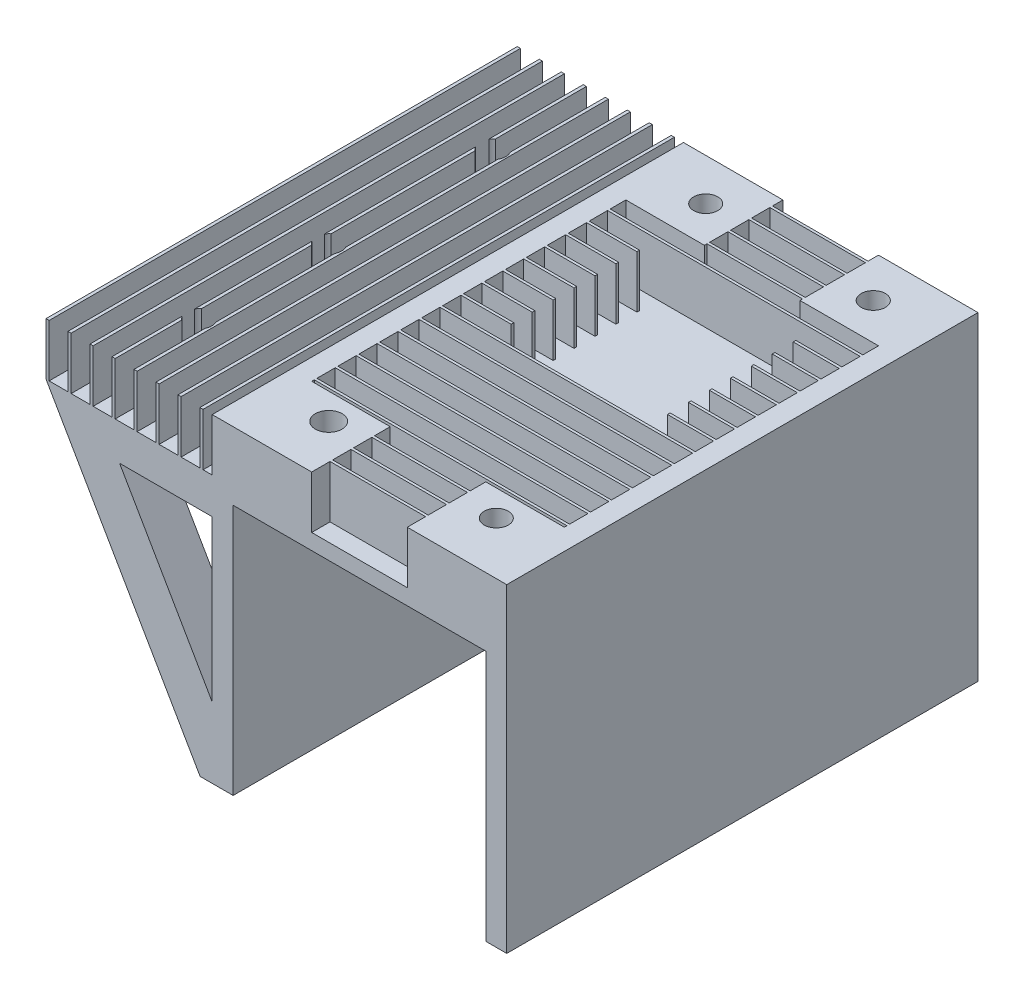
SolidWorks part; units mm, degrees
ref_plane "Front" through (0, 0, 0) normal (0, 0, 1) x (1, 0, 0)
ref_plane "Top" through (0, 0, 0) normal (0, 1, 0) x (1, 0, 0)
ref_plane "Right" through (0, 0, 0) normal (1, 0, 0) x (0, 0, -1)
sketch "Sketch1" plane through (0, 0, 0) normal (0, 0, 1) x (1, 0, 0)
  line L0 (0, 0) -> (0, 70)
  line L1 (0, 70) -> (56.254, 70)
  line L2 (56.254, 70) -> (56.254, 0)
  line L3 (56.254, 0) -> (52.254, 0)
  line L4 (52.254, 0) -> (52.254, 65)
  line L5 (52.254, 65) -> (4, 65)
  line L6 (4, 65) -> (4, 0)
  line L7 (4, 0) -> (0, 0)
  line L9 (4, 55) -> (52.254, 55)
  line L10 (4, 55) -> (4, 52)
  line L11 (4, 52) -> (52.254, 52)
  line L12 (52.254, 55) -> (52.254, 52)
  dimension "D1" = 48.254
  dimension "D2" = 4
  dimension "D3" = 4
  dimension "D4" = 5
  dimension "D5" = 70
  dimension "D6" = 3
  dimension "D7" = 10
extrude "Boss-Extrude1" add sketch "Sketch1" along normal blind 70 contours L7 L6 L5 L4 L3 L2 L1 L0 | L9 L12 L11 L10 region at (0.898, 35, 0)
sketch "Sketch3" plane through (0, 0, 70) normal (0, 0, 1) x (1, 0, 0)
  line L0 (0, 70) -> (-40.3946, 70)
  line L1 (-40.3946, 70) -> (0, 0.0344)
  line L2 (0, 0) -> (0, 70) construction
  line L3 (0, 0.0344) -> (0, 70)
  line L4 (0, 70) -> (0, 62.5)
  line L5 (0, 62.5) -> (-26, 62.5)
  line L6 (-26, 62.5) -> (0, 17.4667)
  line L7 (0, 17.4667) -> (0, 0.0344)
  line M11 (0, 70) -> (0, 0)
  dimension "D1" = 60
  dimension "D2" = 180
  dimension "D3" = 7.5
  dimension "D4" = 26
extrude "Boss-Extrude3" add sketch "Sketch3" against normal blind 8 contours L6 L5 L0 L1 M11 region at (-16.8587, 46.1047, 70)
sketch "Sketch4" plane through (0, 0, 0) normal (0, 0, -1) x (-1, 0, 0)
  line L0 (0, 70) -> (40.3946, 70)
  line L1 (40.3946, 70) -> (0, 0)
  line L2 (0, 0) -> (0, 17.4667)
  line L3 (0, 17.4667) -> (26, 62.5)
  line L4 (26, 62.5) -> (0, 62.5)
  line L5 (0, 62.5) -> (0, 70)
extrude "Boss-Extrude4" add sketch "Sketch4" against normal blind 8
ref_plane "Plane1" through (0, 0, 39) normal (0, 0, -1) x (-1, 0, 0)
sketch "Sketch5" plane through (0, 0, 39) normal (0, 0, -1) x (-1, 0, 0)
  line L0 (0, 62.5) -> (0, 70)
  line L1 (0, 70) -> (40.3946, 70)
  line L2 (40.3946, 70) -> (0, 0)
  line L3 (0, 0) -> (0, 17.4667)
  line L4 (0, 17.4667) -> (26, 62.5)
  line L5 (26, 62.5) -> (0, 62.5)
extrude "Boss-Extrude5" add sketch "Sketch5" along normal blind 8
sketch "Sketch6" plane through (0, 0, 0) normal (0, 0, -1) x (-1, 0, 0)
  line L5 (0, 62.5) -> (36.0666, 62.5)
  line L6 (0, 0) -> (40.3946, 70) construction
  line L7 (36.0666, 62.5) -> (40.3946, 70)
  line L8 (40.3946, 70) -> (0, 70)
  line L9 (40.3946, 70) -> (-56.254, 70) construction
  line L10 (0, 70) -> (0, 62.5)
  line L11 (-4, 0) -> (0, 0)
  line L12 (0, 0) -> (7.5019, 13)
  line L13 (7.5019, 13) -> (-4, 13)
  line L14 (-4, 52) -> (-4, 0) construction
  line L15 (-4, 13) -> (-4, 0)
  dimension "D1" = 13
extrude "Boss-Extrude6" add sketch "Sketch6" against normal blind 70
sketch "Sketch7" plane through (0, 0, 70) normal (0, 0, 1) x (1, 0, 0)
  line L0 (0, 17.4667) -> (0, 62.5) construction
  line L1 (-40.3946, 70) -> (0, 70)
  line L2 (-40.3946, 70) -> (-40.3946, 53)
  line L3 (-40.3946, 53) -> (0, 53)
  line L4 (0, 70) -> (0, 53)
  dimension "D1" = 17
extrude "Cut-Extrude3" cut sketch "Sketch7" against normal blind 70
sketch "Sketch8" plane through (0, 0, 0) normal (0, 0, -1) x (-1, 0, 0)
  line L1 (-4, 55) -> (-4, 52)
  line L2 (-4, 52) -> (-52.254, 52) construction
  line L3 (-4, 52) -> (30.0074, 52)
  line L4 (0, 0) -> (30.5845, 53) construction
  line L6 (30.0074, 52) -> (31.7386, 55)
  line L7 (31.7386, 55) -> (-4, 55)
  dimension "D1" = 180
extrude "Boss-Extrude7" add sketch "Sketch8" against normal blind 70
sketch "Sketch11" plane through (0, 0, 70) normal (0, 0, 1) x (1, 0, 0)
  line L0 (-31.7386, 55) -> (0, 0)
  line L3 (-31.7386, 55) -> (0, 55) construction
  line L4 (-27.289, 55) -> (-31.7386, 55)
  line L5 (-27.289, 55) -> (-3.0537, 13)
  line L6 (-3.0537, 13) -> (0, 0)
extrude "Boss-Extrude10" add sketch "Sketch11" against normal blind 8
sketch "Sketch12" plane through (0, 0, 70) normal (0, 0, 1) x (1, 0, 0)
  line L0 (-31.7386, 55) -> (-27.7598, 48.1051)
  line L1 (0, 0) -> (-31.7386, 55) construction
  line L2 (-27.7598, 48.1051) -> (0, 48.1051)
  line L3 (0, 17.4667) -> (0, 52) construction
  line L4 (0, 48.1051) -> (0, 55)
  line L5 (0, 55) -> (-31.7386, 55)
extrude "Boss-Extrude11" add sketch "Sketch12" against normal blind 70
sketch "Sketch13" plane through (0, 0, 0) normal (0, -1, 0) x (1, 0, 0)
  line L1 (67.4394, -10.6205) -> (-15.562, -10.6205)
  line L2 (67.4394, -10.6205) -> (67.4394, 77.2481)
  line L3 (67.4394, 77.2481) -> (-15.562, 77.2481)
  line L4 (-15.562, -10.6205) -> (-15.562, 77.2481)
extrude "Cut-Extrude4" cut sketch "Sketch13" against normal blind 4
sketch "Sketch14" plane through (0, 0, 70) normal (0, 0, 1) x (1, 0, 0)
  line L0 (-2.3083, 4) -> (-31.7386, 55)
  line L1 (-31.7386, 55) -> (0, 55)
  line L2 (0, 55) -> (0, 70)
  line L3 (0, 70) -> (56.254, 70)
  line L4 (56.254, 70) -> (56.254, 4)
  line L5 (56.254, 4) -> (52.254, 4)
  line L6 (52.254, 4) -> (52.254, 52)
  line L7 (52.254, 52) -> (4, 52)
  line L8 (4, 52) -> (4, 4)
  line L9 (4, 4) -> (-2.3083, 4)
  line L14 (-17.6891, 48.1051) -> (0, 48.1051)
  line L15 (52.254, 55) -> (4, 55)
  line L16 (52.254, 55) -> (52.254, 65)
  line L17 (52.254, 65) -> (4, 65)
  line L18 (4, 55) -> (4, 65)
  line L19 (-17.6891, 48.1051) -> (0, 48.1051) construction
  line L20 (0, 48.1051) -> (0, 17.4667)
  line L21 (0, 17.4667) -> (-17.6891, 48.1051)
extrude "Boss-Extrude12" add sketch "Sketch14" along normal blind 20
sketch "Sketch15" plane through (0, 0, 90) normal (0, 0, 1) x (1, 0, 0)
  line L0 (56.254, 4) -> (56.254, 70) construction
  line L1 (56.254, 65) -> (37.264, 65)
  line L2 (56.254, 65) -> (56.254, 55)
  line L3 (56.254, 55) -> (37.264, 55)
  line L4 (37.264, 65) -> (37.264, 55)
  line L5 (4, 55) -> (52.254, 55) construction
  dimension "D1" = 18.99
sketch "Sketch16" plane through (0, 0, 90) normal (0, 0, 1) x (1, 0, 0)
  line L1 (0, 70) -> (56.254, 70)
  line L2 (0, 70) -> (0, 65)
  line L3 (0, 65) -> (56.254, 65)
  line L4 (56.254, 70) -> (56.254, 65)
extrude "Cut-Extrude5" cut sketch "Sketch16" against normal blind 100
sketch "Sketch17" plane through (0, 65, 0) normal (0, 1, 0) x (1, 0, 0)
  line L1 (52.254, 0) -> (37.254, 0)
  line L2 (52.254, 0) -> (52.254, -15)
  line L3 (52.254, -15) -> (37.254, -15)
  line L4 (37.254, 0) -> (37.254, -15)
  line L5 (52.254, -90) -> (37.254, -90)
  line L6 (52.254, -90) -> (52.254, -75)
  line L7 (52.254, -75) -> (37.254, -75)
  line L8 (37.254, -90) -> (37.254, -75)
  dimension "D1" = 15
  dimension "D2" = 15
  dimension "D3" = 15
  dimension "D4" = 15
extrude "Boss-Extrude14" add sketch "Sketch17" against normal blind 13
sketch "Sketch21" plane through (0, 52, 0) normal (0, -1, 0) x (-1, 0, 0)
  circle A0 centre (-44.254, -80) radius 2.3
  circle A1 centre (-44.254, -8) radius 2.3
sketch "Sketch22" plane through (0, 52, 0) normal (0, -1, 0) x (1, 0, 0)
  line L1 (48.0965, 6.0036) -> (47.9041, 10.3295)
  line L2 (47.9041, 10.3295) -> (44.0617, 12.3259)
  line L3 (44.0617, 12.3259) -> (40.4115, 9.9964)
  line L4 (40.4115, 9.9964) -> (40.6039, 5.6705)
  line L5 (40.6039, 5.6705) -> (44.4463, 3.6741)
  line L6 (44.4463, 3.6741) -> (48.0965, 6.0036)
  line L7 (45.2007, 75.7746) -> (48.3866, 78.7072)
  line L8 (48.3866, 78.7072) -> (47.4399, 82.9325)
  line L9 (47.4399, 82.9325) -> (43.3073, 84.2254)
  line L10 (43.3073, 84.2254) -> (40.1214, 81.2928)
  line L11 (40.1214, 81.2928) -> (41.0681, 77.0675)
  line L12 (41.0681, 77.0675) -> (45.2007, 75.7746)
  circle A0 centre (44.254, 8) radius 3.75 construction
  circle A1 centre (44.254, 80) radius 3.75 construction
  point P10 (42.2366, 11.1611)
  dimension "D1" = 7.5
  dimension "D2" = 7.5
extrude "Cut-Extrude8" cut sketch "Sketch22" against normal blind 5
extrude "Cut-Extrude9" cut sketch "Sketch21" against normal blind 15
sketch "Sketch23" plane through (0, 0, 0) normal (-0.8661, -0.4998, 0) x (0, 0, 1)
  line L0 (90, 63.5007) -> (90, 4.6182) construction
  line L1 (70, 55.5401) -> (82, 55.5401)
  line L2 (70, 55.5401) -> (70, 15.0093)
  line L3 (70, 15.0093) -> (82, 15.0093)
  line L4 (82, 55.5401) -> (82, 15.0093)
  line L5 (62, 55.5401) -> (62, 15.0093) construction
  dimension "D1" = 8
  dimension "D2" = 8
extrude "Cut-Extrude10" cut sketch "Sketch23" against normal blind 9
sketch "Sketch25" plane through (0, 48.1051, 0) normal (0, -1, 0) x (-1, 0, 0)
  circle A0 centre (17.0755, -19.3006) radius 2.3
  circle A1 centre (17.0755, -50.6137) radius 2.3
extrude "Cut-Extrude11" cut sketch "Sketch25" against normal blind 20
sketch "Sketch26" plane through (0, 48.1051, 0) normal (0, -1, 0) x (1, 0, 0)
  circle A0 centre (-17.0755, 75.3913) radius 2.3
extrude "Cut-Extrude12" cut sketch "Sketch26" against normal blind 20
sketch "Sketch27" plane through (0, 0, 90) normal (0, 0, 1) x (1, 0, 0)
  line L0 (-23.3104, 48.1051) -> (-27.7598, 48.1051)
  line L1 (-31.7386, 55) -> (-2.3083, 4) construction
  line L2 (-27.7598, 48.1051) -> (-31.7386, 55)
  line L3 (-31.7386, 55) -> (-23.3104, 55)
  line L4 (0, 55) -> (-31.7386, 55) construction
  line L5 (-23.3104, 55) -> (-23.3104, 48.1051)
extrude "Boss-Extrude16" add sketch "Sketch27" against normal blind 20
sketch "Sketch28" plane through (0, 55, 0) normal (0, 1, 0) x (1, 0, 0)
  line L0 (4, -90) -> (37.254, -90) construction
  line L1 (4, 0) -> (19, 0)
  line L2 (4, 0) -> (4, -15)
  line L3 (4, -15) -> (19, -15)
  line L4 (19, 0) -> (19, -15)
  line L5 (4, -90) -> (19, -90)
  line L6 (4, -90) -> (4, -75)
  line L7 (4, -75) -> (19, -75)
  line L8 (19, -90) -> (19, -75)
  line L9 (4, 0) -> (4, -90) construction
  dimension "D1" = 15
  dimension "D2" = 15
  dimension "D3" = 15
  dimension "D4" = 15
extrude "Boss-Extrude17" add sketch "Sketch28" along normal blind 10
sketch "Sketch29" plane through (0, 52, 0) normal (0, -1, 0) x (-1, 0, 0)
  circle A0 centre (-12.254, -8) radius 2.3
  circle A1 centre (-12.254, -80) radius 2.3
extrude "Cut-Extrude13" cut sketch "Sketch29" against normal blind 20
sketch "Sketch30" plane through (0, 48.1051, 0) normal (0, -1, 0) x (1, 0, 0)
  line L1 (-27.7598, 70) -> (-17.3688, 70)
  line L2 (-27.7598, 70) -> (-27.7598, 82)
  line L3 (-27.7598, 82) -> (-17.3688, 82)
  line L4 (-17.3688, 70) -> (-17.3688, 82)
extrude "Boss-Extrude18" add sketch "Sketch30" against normal blind 5
sketch "Sketch31" plane through (0, 48.1051, 0) normal (0, -1, 0) x (1, 0, 0)
  circle A0 centre (-17.0755, 75.3913) radius 2.3
extrude "Cut-Extrude14" cut sketch "Sketch31" against normal blind 45
sketch "Sketch36" plane through (0, 55, 0) normal (0, 1, 0) x (1, 0, 0)
  line L0 (0, -90) -> (-31.7386, -90) construction
  line L1 (-31.7386, 0) -> (-31.1386, 0)
  line L2 (-31.7386, 0) -> (-31.7386, -90)
  line L3 (-31.7386, -90) -> (-31.1386, -90)
  line L4 (-31.1386, 0) -> (-31.1386, -90)
  line L5 (-27.5386, 0) -> (-27.5386, -90)
  line L6 (-27.5386, 0) -> (-26.9386, 0)
  line L7 (-26.9386, 0) -> (-26.9386, -90)
  line L8 (-27.5386, -90) -> (-26.9386, -90)
  line L9 (-23.3386, 0) -> (-23.3386, -90)
  line L10 (-23.3386, 0) -> (-22.7386, 0)
  line L11 (-22.7386, 0) -> (-22.7386, -90)
  line L12 (-23.3386, -90) -> (-22.7386, -90)
  line L13 (-19.1386, 0) -> (-19.1386, -90)
  line L14 (-19.1386, 0) -> (-18.5386, 0)
  line L15 (-18.5386, 0) -> (-18.5386, -90)
  line L16 (-19.1386, -90) -> (-18.5386, -90)
  line L17 (-14.9386, 0) -> (-14.9386, -90)
  line L18 (-14.9386, 0) -> (-14.3386, 0)
  line L19 (-14.3386, 0) -> (-14.3386, -90)
  line L20 (-14.9386, -90) -> (-14.3386, -90)
  line L21 (-10.7386, 0) -> (-10.7386, -90)
  line L22 (-10.7386, 0) -> (-10.1386, 0)
  line L23 (-10.1386, 0) -> (-10.1386, -90)
  line L24 (-10.7386, -90) -> (-10.1386, -90)
  line L25 (-6.5386, 0) -> (-6.5386, -90)
  line L26 (-6.5386, 0) -> (-5.9386, 0)
  line L27 (-5.9386, 0) -> (-5.9386, -90)
  line L28 (-6.5386, -90) -> (-5.9386, -90)
  line L29 (-2.3386, 0) -> (-2.3386, -90)
  line L30 (-2.3386, 0) -> (-1.7386, 0)
  line L31 (-1.7386, 0) -> (-1.7386, -90)
  line L32 (-2.3386, -90) -> (-1.7386, -90)
  line L33 (-31.7386, 0) -> (-27.5386, 0) construction
  dimension "D1" = 0.6
  dimension "D3" = 4.2
  dimension "D2" = 8
extrude "Boss-Extrude19" add sketch "Sketch36" along normal blind 10
sketch "Sketch37" plane through (0, 55, 0) normal (0, 1, 0) x (1, 0, 0)
  line L0 (19, 0) -> (37.254, 0) construction
  line L13 (4, -6) -> (4, -6.5)
  line L14 (4, -15) -> (4, -75) construction
  line L15 (4, -2) -> (53, -2)
  line L16 (4, -2) -> (4, -2.5)
  line L17 (4, -2.5) -> (53, -2.5)
  line L18 (53, -2) -> (53, -2.5)
  line L19 (4, -6) -> (53, -6)
  line L20 (53, -6) -> (53, -6.5)
  line L21 (4, -6.5) -> (53, -6.5)
  line L22 (4, -10) -> (4, -10.5)
  line L23 (4, -10) -> (53, -10)
  line L24 (53, -10) -> (53, -10.5)
  line L25 (4, -10.5) -> (53, -10.5)
  line L26 (4, -14) -> (4, -14.5)
  line L27 (4, -14) -> (53, -14)
  line L28 (53, -14) -> (53, -14.5)
  line L29 (4, -14.5) -> (53, -14.5)
  line L30 (4, -18) -> (4, -18.5)
  line L31 (4, -18) -> (53, -18)
  line L32 (53, -18) -> (53, -18.5)
  line L33 (4, -18.5) -> (53, -18.5)
  line L34 (4, -22) -> (4, -22.5)
  line L35 (4, -22) -> (53, -22)
  line L36 (53, -22) -> (53, -22.5)
  line L37 (4, -22.5) -> (53, -22.5)
  line L38 (4, -26) -> (4, -26.5)
  line L39 (4, -26) -> (53, -26)
  line L40 (53, -26) -> (53, -26.5)
  line L41 (4, -26.5) -> (53, -26.5)
  line L42 (4, -30) -> (4, -30.5)
  line L43 (4, -30) -> (53, -30)
  line L44 (53, -30) -> (53, -30.5)
  line L45 (4, -30.5) -> (53, -30.5)
  line L46 (4, -34) -> (4, -34.5)
  line L47 (4, -34) -> (53, -34)
  line L48 (53, -34) -> (53, -34.5)
  line L49 (4, -34.5) -> (53, -34.5)
  line L50 (4, -38) -> (4, -38.5)
  line L51 (4, -38) -> (53, -38)
  line L52 (53, -38) -> (53, -38.5)
  line L53 (4, -38.5) -> (53, -38.5)
  line L54 (4, -42) -> (4, -42.5)
  line L55 (4, -42) -> (53, -42)
  line L56 (53, -42) -> (53, -42.5)
  line L57 (4, -42.5) -> (53, -42.5)
  line L58 (4, -46) -> (4, -46.5)
  line L59 (4, -46) -> (53, -46)
  line L60 (53, -46) -> (53, -46.5)
  line L61 (4, -46.5) -> (53, -46.5)
  line L62 (4, -50) -> (4, -50.5)
  line L63 (4, -50) -> (53, -50)
  line L64 (53, -50) -> (53, -50.5)
  line L65 (4, -50.5) -> (53, -50.5)
  line L66 (4, -54) -> (4, -54.5)
  line L67 (4, -54) -> (53, -54)
  line L68 (53, -54) -> (53, -54.5)
  line L69 (4, -54.5) -> (53, -54.5)
  line L70 (4, -58) -> (4, -58.5)
  line L71 (4, -58) -> (53, -58)
  line L72 (53, -58) -> (53, -58.5)
  line L73 (4, -58.5) -> (53, -58.5)
  line L74 (4, -62) -> (4, -62.5)
  line L75 (4, -62) -> (53, -62)
  line L76 (53, -62) -> (53, -62.5)
  line L77 (4, -62.5) -> (53, -62.5)
  line L78 (4, -66) -> (4, -66.5)
  line L79 (4, -66) -> (53, -66)
  line L80 (53, -66) -> (53, -66.5)
  line L81 (4, -66.5) -> (53, -66.5)
  line L82 (4, -70) -> (4, -70.5)
  line L83 (4, -70) -> (53, -70)
  line L84 (53, -70) -> (53, -70.5)
  line L85 (4, -70.5) -> (53, -70.5)
  line L86 (4, -74) -> (4, -74.5)
  line L87 (4, -74) -> (53, -74)
  line L88 (53, -74) -> (53, -74.5)
  line L89 (4, -74.5) -> (53, -74.5)
  line L90 (4, -78) -> (4, -78.5)
  line L91 (4, -78) -> (53, -78)
  line L92 (53, -78) -> (53, -78.5)
  line L93 (4, -78.5) -> (53, -78.5)
  line L94 (4, -82) -> (4, -82.5)
  line L95 (4, -82) -> (53, -82)
  line L96 (53, -82) -> (53, -82.5)
  line L97 (4, -82.5) -> (53, -82.5)
  line L98 (4, -86) -> (4, -86.5)
  line L99 (4, -86) -> (53, -86)
  line L100 (53, -86) -> (53, -86.5)
  line L101 (4, -86.5) -> (53, -86.5)
  dimension "D1" = 49
  dimension "D2" = 0.5
  dimension "D3" = 2
  dimension "D4" = 22
extrude "Boss-Extrude20" add sketch "Sketch37" along normal blind 10
sketch "Sketch39" plane through (0, 65, 0) normal (0, 1, 0) x (1, 0, 0)
  line L1 (13.6092, -19.7718) -> (43.455, -19.7718)
  line L2 (13.6092, -19.7718) -> (13.6092, -48.773)
  line L3 (13.6092, -48.773) -> (43.455, -48.773)
  line L4 (43.455, -19.7718) -> (43.455, -48.773)
  circle A0 centre (12.254, -8) radius 2.3
  circle A1 centre (44.254, -8) radius 2.3
  circle A2 centre (-17.0755, -19.3006) radius 2.4421
  circle A3 centre (-17.0755, -50.6137) radius 2.2138
  circle A4 centre (-17.0755, -75.3913) radius 2.3
  circle A5 centre (12.254, -80) radius 2.3
  circle A6 centre (44.254, -80) radius 2.3
extrude "Cut-Extrude15" cut sketch "Sketch39" against normal blind 10
sketch "Sketch40" plane through (0, 65, 0) normal (0, 1, 0) x (1, 0, 0)
  circle A0 centre (-17.0755, -19.3006) radius 2.2732
  circle A1 centre (-17.0755, -50.6137) radius 2.3827
  circle A2 centre (-17.0755, -75.3913) radius 2.3828
  circle A3 centre (12.254, -80) radius 2.5607
  circle A4 centre (44.254, -80) radius 2.2791
  circle A5 centre (44.254, -8) radius 2.3112
  circle A6 centre (12.254, -8) radius 2.3
extrude "Cut-Extrude16" cut sketch "Sketch40" against normal blind 30
